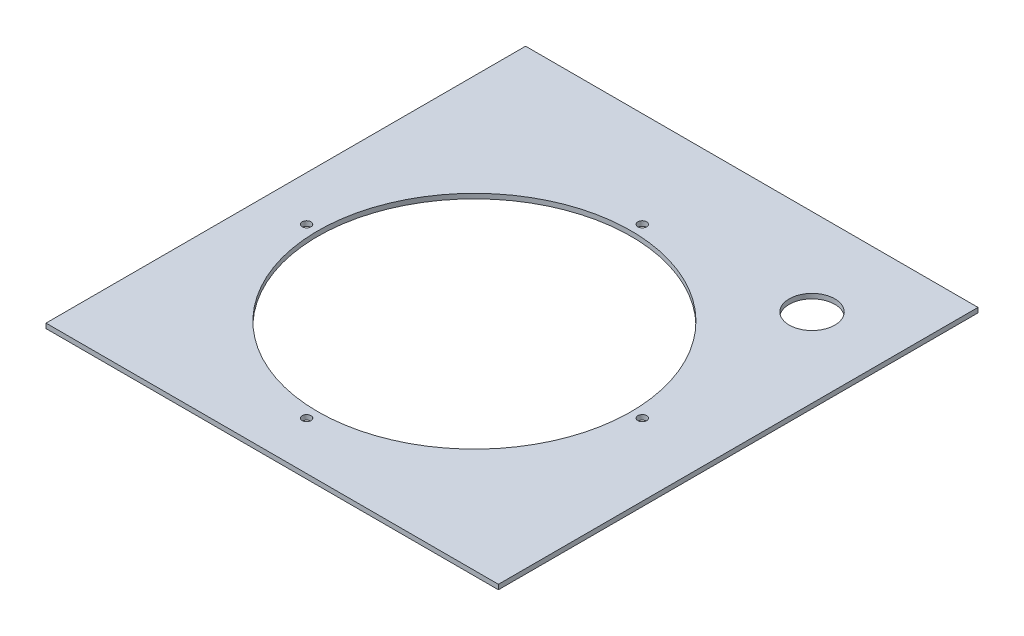
SolidWorks part; units mm, degrees
ref_plane "Front Plane" through (0, 0, 0) normal (0, 0, 1) x (1, 0, 0)
ref_plane "Top Plane" through (0, 0, 0) normal (0, 1, 0) x (1, 0, 0)
ref_plane "Right Plane" through (0, 0, 0) normal (1, 0, 0) x (0, 0, -1)
sketch "Sketch1" plane through (0, 0, 0) normal (0, 1, 0) x (1, 0, 0)
  line L1 (0, 0) -> (300, 0)
  line L2 (0, 0) -> (0, -330)
  line L3 (0, -330) -> (300, -330)
  line L4 (300, 0) -> (300, -330)
  dimension "D1" = 300
  dimension "D2" = 330
extrude "Boss-Extrude1" add sketch "Sketch1" along normal blind 3
sketch "Sketch2" plane through (0, 3, 0) normal (0, 1, 0) x (1, 0, 0)
  line L0 (300, -330) -> (300, 0) construction
  line L1 (0, -330) -> (300, -330) construction
  line L2 (150, -165) -> (300, 0) construction
  line L3 (300, 0) -> (300, -330) construction
  line L4 (0, 0) -> (300, 0) construction
  circle A0 centre (150, -165) radius 98
  circle A1 centre (250.5646, -54.379) radius 14.255
  point P5 (300, -165)
  point P8 (150, -330)
  dimension "D1" = 196
  dimension "D3" = 28.51
  dimension "D2" = 149.5
  dimension "D4" = 49.4354
  dimension "D5" = 54.379
extrude "Cut-Extrude1" cut sketch "Sketch2" against normal up to next
sketch "Sketch4" plane through (0, 3, 0) normal (0, 1, 0) x (1, 0, 0)
  line L0 (0, -330) -> (300, -330) construction
  line L1 (0, 0) -> (0, -330) construction
  line L2 (300, 0) -> (300, -330) construction
  line L3 (0, 0) -> (300, 0) construction
  circle A0 centre (150, -165) radius 105 construction
  circle A2 centre (45, -165) radius 2.75
  circle A3 centre (255, -165) radius 2.75
  circle A4 centre (150, -270) radius 2.75
  circle A5 centre (150, -60) radius 2.75
  dimension "D1" = 210
  dimension "D2" = 5.5
  dimension "D3" = 5.5
  dimension "D4" = 5.5
  dimension "D5" = 5.5
  dimension "D7" = 45
  dimension "D8" = 45
  dimension "D9" = 60
  dimension "D6" = 60
extrude "Cut-Extrude3" cut sketch "Sketch4" against normal through all contours A2 | A5 | A3 | A4
sketch "Sketch5" plane through (0, 3, 0) normal (0, 1, 0) x (1, 0, 0)
  line L0 (300, -330) -> (300, 0) construction
  line L1 (0, 0) -> (300, 0)
  line L2 (0, 0) -> (0, -300)
  line L3 (0, -300) -> (300, -300)
  line L4 (300, 0) -> (300, -300)
  line L5 (0, -330) -> (300, -330) construction
  dimension "D1" = 30
sketch "Sketch6" plane through (0, 3, 0) normal (0, 1, 0) x (1, 0, 0)
  line L0 (300, -330) -> (300, 0) construction
  line L1 (0, -330) -> (300, -330)
  line L2 (0, -330) -> (0, -300)
  line L3 (0, -300) -> (300, -300)
  line L4 (300, -330) -> (300, -300)
  dimension "D1" = 30
extrude "Cut-Extrude5" cut sketch "Sketch6" against normal through all
sketch "Sketch7" plane through (0, 3, 0) normal (0, 1, 0) x (1, 0, 0)
  line L0 (300, -300) -> (0, -300) construction
  line L1 (0, 0) -> (17, 0)
  line L2 (0, 0) -> (0, -300)
  line L3 (0, -300) -> (17, -300)
  line L4 (17, 0) -> (17, -300)
  point P6 (0, 0)
  point P8 (0, 0)
  point P9 (39.3908, 0)
  dimension "D1" = 17
extrude "Cut-Extrude6" cut sketch "Sketch7" against normal through all
